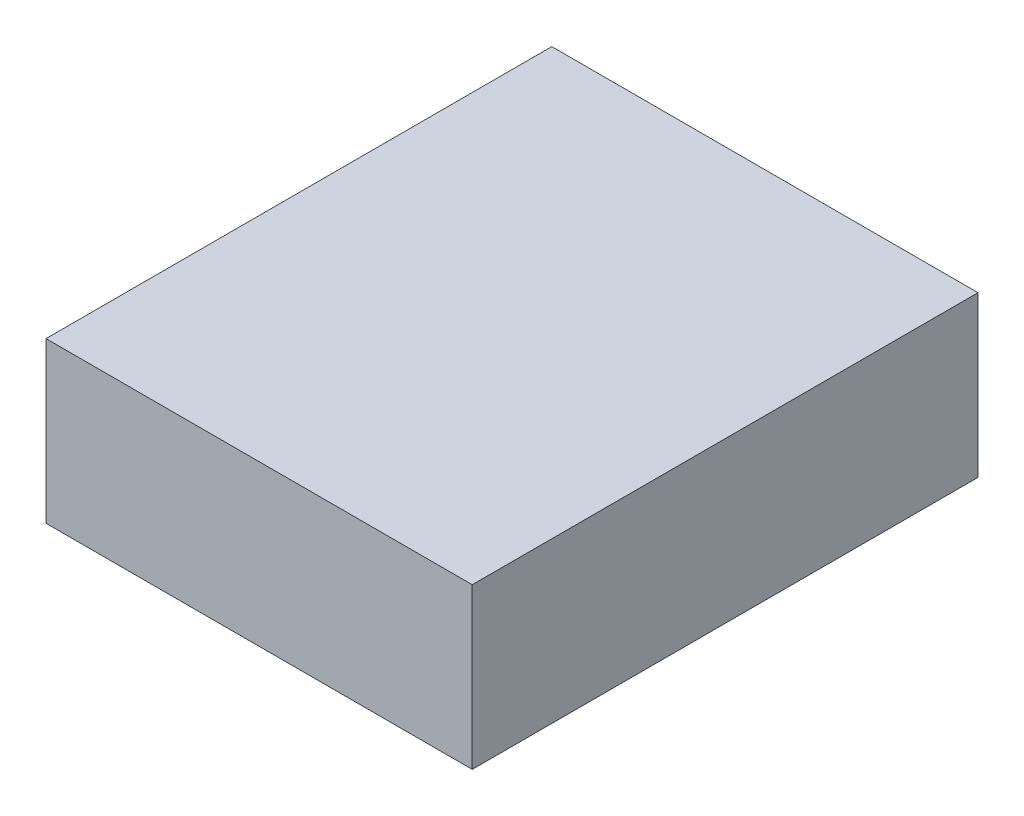
SolidWorks part; units mm, degrees
ref_plane "Front Plane" through (0, 0, 0) normal (0, 0, 1) x (1, 0, 0)
ref_plane "Top Plane" through (0, 0, 0) normal (0, 1, 0) x (1, 0, 0)
ref_plane "Right Plane" through (0, 0, 0) normal (1, 0, 0) x (0, 0, -1)
sketch "pilotSketch_base" plane through (0, 0, 0) normal (0, 1, 0) x (1, 0, 0)
  line L0 (-5, 5) -> (5, -5) construction
  line L1 (-5, -5) -> (5, 5) construction
  line L2 (0, 0) -> (6.6791, 0) construction
  point P5 (0, 0)
  dimension "D1" = 10
ref_plane "Plane1" through (0, 0, 0) normal (0.7071, 0, 0.7071) x (0.7071, 0, -0.7071)
sketch "pilotSketch_angle" plane through (0, 0, 0) normal (0.7071, 0, 0.7071) x (0.7071, 0, -0.7071)
  line L0 (-7.0711, 0) -> (-4.3883, 2.6827) construction
  line L4 (-7.0711, 0) -> (7.0711, 0) construction
  dimension "D1" = 45
ref_plane "Plane2" through (-5, 0, 5) normal (0.5, 0.7071, -0.5) x (0.866, -0.4082, 0.2887)
ref_plane "Plane3" through (0, 0, 5) normal (0, 0, 1) x (1, 0, 0)
ref_plane "Plane4" through (-5, 0, 0) normal (1, 0, 0) x (0, 0, -1)
sketch "Sketch1" plane through (0, 0, 0) normal (0, 1, 0) x (1, 0, 0)
  line L1 (-10.4778, 16.4005) -> (16.1702, 16.4005)
  line L2 (-10.4778, 16.4005) -> (-10.4778, -15.219)
  line L3 (-10.4778, -15.219) -> (16.1702, -15.219)
  line L4 (16.1702, 16.4005) -> (16.1702, -15.219)
extrude "pierceablePlane" add sketch "Sketch1" against normal blind 10
